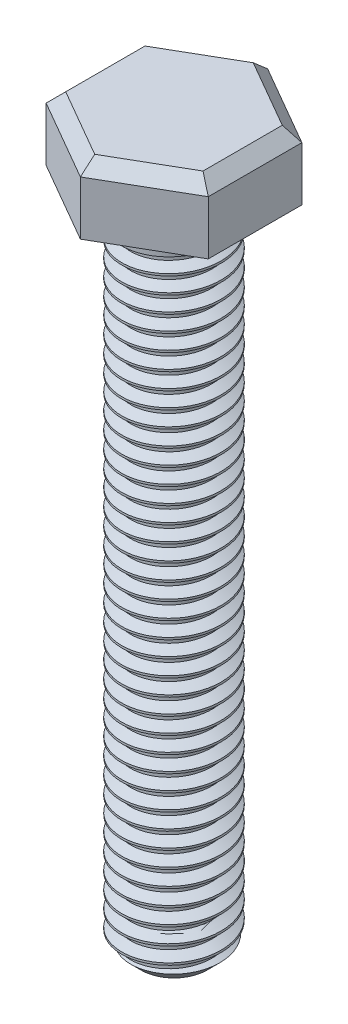
SolidWorks part; units mm, degrees
ref_plane "Plano frontal" through (0, 0, 0) normal (0, 0, 1) x (1, 0, 0)
ref_plane "Plano superior" through (0, 0, 0) normal (0, 1, 0) x (1, 0, 0)
ref_plane "Plano direito" through (0, 0, 0) normal (1, 0, 0) x (0, 0, -1)
sketch "Esboço1" plane through (0, 0, 0) normal (0, 1, 0) x (1, 0, 0)
  line L1 (0, 5.6465) -> (-4.89, 2.8232)
  line L2 (-4.89, 2.8232) -> (-4.89, -2.8232)
  line L3 (-4.89, -2.8232) -> (0, -5.6465)
  line L4 (0, -5.6465) -> (4.89, -2.8232)
  line L5 (4.89, -2.8232) -> (4.89, 2.8232)
  line L6 (4.89, 2.8232) -> (0, 5.6465)
  circle A0 centre (0, 0) radius 4.89 construction
  dimension "D1" = 9.78
extrude "Ressalto-extrusão1" add sketch "Esboço1" along normal mid plane 4
sketch "Esboço2" plane through (0, -2, 0) normal (0, -1, 0) x (1, 0, 0)
  circle A0 centre (0, 0) radius 3
  dimension "D1" = 6
extrude "Ressalto-extrusão2" add sketch "Esboço2" along normal blind 40
fillet "Filete1" radius 1 1 edges at (0, -2, -3)
chamfer "Chanfro1" distance 1 angle 45 1 edges at (0, -42, -3)
thread "Rosca1" pitch 1 method cut profile "Perfil da rosca1" start angle 0, offset 0, length 0, pitch 1, diameter 6
ref_plane "Plano1" through (-3, -3, 0) normal (0, 0, 1) x (-1, 0, 0)
sketch "Perfil da rosca1" plane through (-3, -3, 0) normal (0, 0, 1) x (-1, 0, 0)
  line L0 (0, 0) -> (0, 1) construction
  line L11 (0, 0) -> (0, 0.875)
  line L12 (0, 0.875) -> (-0.5413, 0.5625)
  line L13 (-0.5413, 0.5625) -> (-0.5413, 0.3125)
  line L15 (-0.5413, 0.3125) -> (0, 0)
  line L17 (-0.5413, 0.4375) -> (0, 0.4375) construction
  point P2 (0, 0)
  dimension "Pitch" = 1
  dimension "Profile_Angle" = 60
  dimension "Profile_Land" = 0.25
  dimension "Profile_Height" = 0.5413
chamfer "Chanfro2" distance 0.75 angle 45 6 edges at (-4.89, 2, 0) (-2.445, 2, -4.2349) (2.445, 2, -4.2349) (4.89, 2, 0) (2.445, 2, 4.2349) (-2.445, 2, 4.2349)
